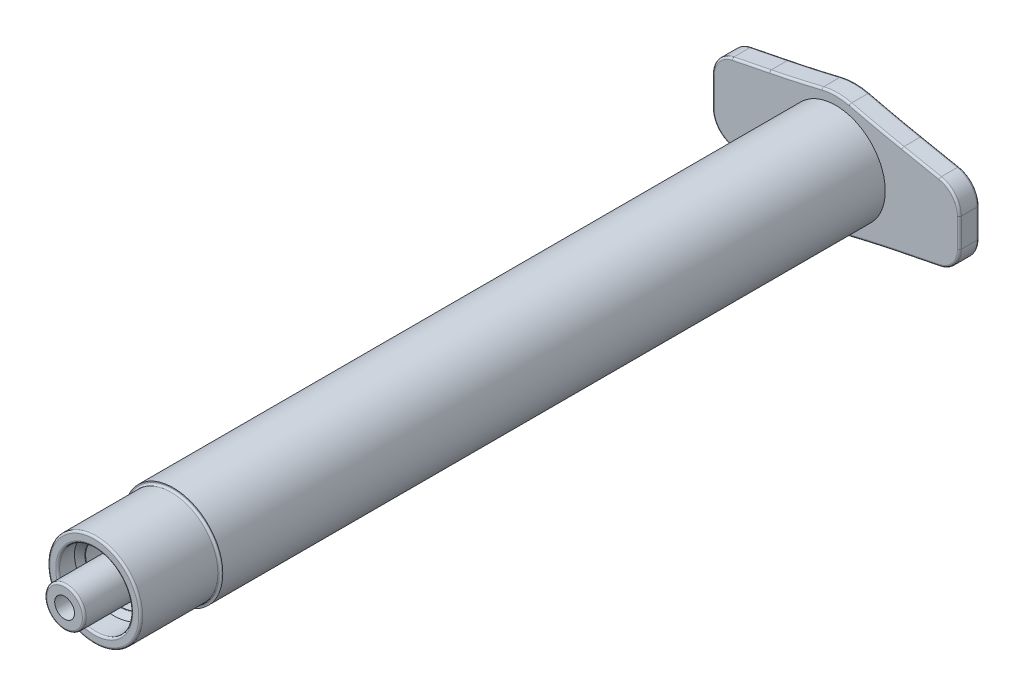
SolidWorks part; units mm, degrees
ref_plane "Front Plane" through (0, 0, 0) normal (0, 0, 1) x (1, 0, 0)
ref_plane "Top Plane" through (0, 0, 0) normal (0, 1, 0) x (1, 0, 0)
ref_plane "Right Plane" through (0, 0, 0) normal (1, 0, 0) x (0, 0, -1)
sketch "Sketch1" plane through (0, 0, 0) normal (0, 0, 1) x (1, 0, 0)
  circle A0 centre (0, 0) radius 5
  dimension "D1" = 10
extrude "Boss-Extrude1" add sketch "Sketch1" along normal blind 68
sketch "Sketch2" plane through (0, 0, 68) normal (0, 0, 1) x (1, 0, 0)
  circle A0 centre (0, 0) radius 4.7
  circle A1 centre (0, 0) radius 5 construction
  dimension "D1" = 0.3
extrude "Boss-Extrude2" add sketch "Sketch2" along normal blind 8
fillet "Fillet3" radius 0.2 1 edges at (4.7, 0, 68)
sketch "Sketch4" plane through (0, 0, 76) normal (0, 0, 1) x (1, 0, 0)
  circle A0 centre (0, 0) radius 3.7
  circle A1 centre (0, 0) radius 4.7 construction
  dimension "D1" = 1
extrude "Cut-Extrude1" cut sketch "Sketch4" against normal blind 8
fillet "Fillet4" radius 0.2 2 edges at (3.7, 0, 76) (4.7, 0, 76)
sketch "Sketch5" plane through (0, 0, 68) normal (0, 0, 1) x (1, 0, 0)
  circle A0 centre (0, 0) radius 3.7
curve "Helix/Spiral1" pitch 3.1111 height 7 turns 2.25
sketch "Sketch8" plane through (0, 0, 0) normal (0, 0, -1) x (-1, 0, 0)
  circle A0 centre (0, 0) radius 4.0054
sketch "Sketch9" plane through (0, 0, 68) normal (0, 0, 1) x (1, 0, 0)
  circle A0 centre (0, 0) radius 2
  circle A1 centre (0, 0) radius 1
  dimension "D1" = 4
  dimension "D2" = 1
extrude "Boss-Extrude4" add sketch "Sketch9" along normal blind 11
fillet "Fillet5" radius 0.2 1 edges at (2, 0, 79)
extrude "Cut-Extrude2" cut sketch "Sketch8" against normal blind 67
sketch "Sketch10" plane through (0, 0, 0) normal (0, 0, -1) x (-1, 0, 0)
  line L0 (12.5, 3.5) -> (2.3077, 5.5385)
  line L2 (-12.5, 3.5) -> (-12.5, -3.5)
  line L4 (12.5, 3.5) -> (12.5, -3.5)
  line L7 (-2.3077, 5.5385) -> (-12.5, 3.5)
  line L8 (-12.5, -3.5) -> (-2.3077, -5.5385)
  line L9 (2.3077, -5.5385) -> (12.5, -3.5)
  circle A0 centre (0, 0) radius 6
  circle A1 centre (0, 0) radius 5 construction
  circle M2 centre (0, 0) radius 5
  dimension "D1" = 1
  dimension "D2" = 25
  dimension "D3" = 7
extrude "Boss-Extrude5" add sketch "Sketch10" along normal mid plane 2 separate body contours A0 L7 L2 L8 | A0 L9 L4 L0 | A0 M2
fillet "Fillet8" radius 132 4 edges at (2.3077, -5.5385, 0) (-2.3077, -5.5385, 0) (2.3077, 5.5385, 0) (-2.3077, 5.5385, 0)
fillet "Fillet9" radius 2.5 4 edges at (-12.5, -3.5, 0) (-12.5, 3.5, 0) (12.5, 3.5, 0) (12.5, -3.5, 0)
fillet "Fillet11" radius 0.2 32 edges at (12.5, 0, -1) (12.5, 0, 1) (11.9334, 3.0355, -1) (11.9334, 3.0355, 1) (8.6018, 4.2796, 1) (8.6018, 4.2796, -1) (4.0594, 5.2165, -1) (4.0594, 5.2165, 1) (0, 6, 1) (0, 6, -1) (-4.0594, 5.2165, -1) (-4.0594, 5.2165, 1) (-8.6018, 4.2796, -1) (-8.6018, 4.2796, 1) (-11.9334, 3.0355, -1) (-11.9334, 3.0355, 1) (-12.5, 0, -1) (-12.5, 0, 1) (-11.9334, -3.0355, -1) (-11.9334, -3.0355, 1) (-8.6018, -4.2796, 1) (-8.6018, -4.2796, -1) (-4.0594, -5.2165, -1) (-4.0594, -5.2165, 1) (0, -6, -1) (0, -6, 1) (4.0594, -5.2165, -1) (4.0594, -5.2165, 1) (8.6018, -4.2796, -1) (8.6018, -4.2796, 1) (11.9334, -3.0355, -1) (11.9334, -3.0355, 1)
sketch "Sketch11" plane through (0, 0, 79) normal (0, 0, 1) x (1, 0, 0)
  circle A0 centre (0, 0) radius 1 construction
  circle A1 centre (0, 0) radius 1
extrude "Cut-Extrude3" cut sketch "Sketch11" against normal blind 12
fillet "Fillet16" radius 0.2 1 edges at (1, 0, 67)
ref_plane "Plane3" through (-2.6163, 2.6163, 68) normal (0.7009, 0.7009, 0.1326) x (0.7133, -0.6869, -0.1393)
sketch "Sketch13" plane through (-2.6163, 2.6163, 68) normal (0.7009, 0.7009, 0.1326) x (0.7133, -0.6869, -0.1393)
  line L1 (0.5891, 0.0354) -> (-0.3308, 0.5665)
  line L2 (-0.3308, 0.5665) -> (-0.3308, -0.5823)
  line L3 (-0.3308, -0.5823) -> (0.5891, -0.0512)
  circle A0 centre (0.0008, -0.0079) radius 0.3316 construction
  arc A1 (0.5891, 0.0354) -> (0.5891, -0.0512) centre (0.5641, -0.0079) cw
  dimension "D1" = 0.05
sweep "Sweep1" add profiles "Sketch13" path "Helix/Spiral1"
